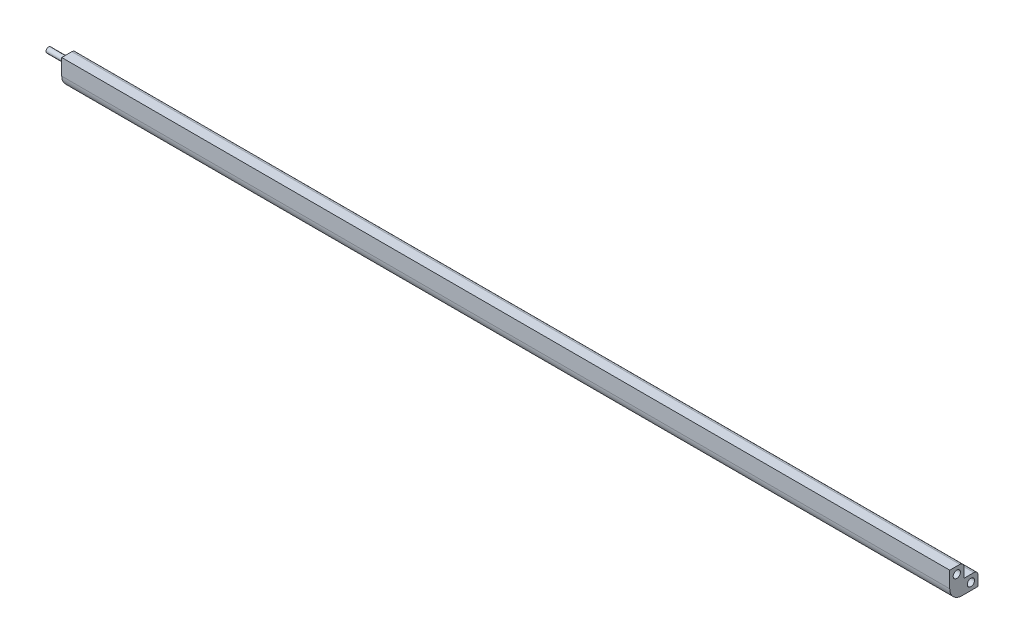
SolidWorks part; units mm, degrees
ref_plane "Front Plane" through (0, 0, 0) normal (0, 0, 1) x (1, 0, 0)
ref_plane "Top Plane" through (0, 0, 0) normal (0, 1, 0) x (1, 0, 0)
ref_plane "Right Plane" through (0, 0, 0) normal (1, 0, 0) x (0, 0, -1)
sketch "Sketch1" plane through (-29.2126, 0, 0) normal (1, 0, 0) x (0, 0, -1)
  line L1 (11.4452, 34.4708) -> (4.4452, 34.4708)
  line L2 (-25.0548, 34.4708) -> (6.4452, 34.4708) construction
  line L3 (4.4452, 34.4708) -> (4.4452, 27.4708)
  line L4 (4.4452, 27.4708) -> (11.4452, 27.4708)
  line L5 (11.4452, 29.4708) -> (11.4452, -30.5292) construction
  line L7 (11.4452, 27.4708) -> (11.4452, 34.4708)
  line L8 (7.9452, 34.4708) -> (7.9452, 30.9708)
  line L9 (7.9452, 30.9708) -> (11.4452, 30.9708)
  circle A0 centre (6.1952, 32.7208) radius 0.65
  circle A1 centre (9.6952, 29.2208) radius 0.65
  circle A2 centre (6.1952, 32.7208) radius 0.9
  circle A3 centre (9.6952, 29.2208) radius 0.9
  line M11 (11.4452, -30.5292) -> (11.4452, 29.4708)
  arc M12 (11.4452, 29.4708) -> (11.2149, 30.9708) centre (6.4452, 29.4708) ccw
  line M13 (6.4452, 34.4708) -> (-25.0548, 34.4708)
  dimension "D5" = 1.3
  dimension "D6" = 1.8
  dimension "D7" = 1.3
  dimension "D8" = 1.8
  dimension "D1" = 7
  dimension "D2" = 7
  dimension "D3" = 1.75
  dimension "D4" = 1.75
  dimension "D9" = 1.75
  dimension "D10" = 1.75
extrude "Boss-Extrude1" add sketch "Sketch1" along normal blind 220 contours L9 L8 L3 L4 A3 A2 M12 M13 M11 | L9 L7 M12 | L8 L1 M12 | A0 | A2 A0 | A3 A1 | A1 region at (-29.2126, 30.2926, -7.2532) region at (-29.2126, 30.5975, -11.3764) region at (-29.2126, 32.7208, -6.1952) region at (-29.2126, 29.2208, -9.6952) region at (-29.2126, 32.7208, -5.3206) region at (-29.2126, 29.2208, -8.8206)
sketch "Sketch2" plane through (190.7874, 0, 0) normal (1, 0, 0) x (0, 0, -1)
  line L0 (11.4452, 34.4708) -> (4.4452, 34.4708)
  line L1 (4.4452, 34.4708) -> (4.4452, 27.4708)
  line L2 (4.4452, 27.4708) -> (11.4452, 27.4708)
  line L3 (11.4452, 27.4708) -> (11.4452, 34.4708)
  line L4 (7.9452, 34.4708) -> (7.9452, 30.9708)
  line L5 (7.9452, 30.9708) -> (11.4452, 30.9708)
  line L6 (7.9452, 34.4708) -> (4.4452, 34.4708) construction
  line L7 (-25.0548, 34.4708) -> (6.4452, 34.4708) construction
  line L8 (11.4452, 27.4708) -> (11.4452, 30.9708) construction
  circle A0 centre (6.1952, 32.7208) radius 0.65
  circle A1 centre (9.6952, 29.2208) radius 0.65
  circle A2 centre (6.1952, 32.7208) radius 0.9
  circle A3 centre (9.6952, 29.2208) radius 0.9
  dimension "D5" = 1.3
  dimension "D6" = 1.8
  dimension "D7" = 1.3
  dimension "D8" = 1.8
  dimension "D1" = 7
  dimension "D2" = 7
  dimension "D3" = 1.75
  dimension "D4" = 1.75
  dimension "D9" = 1.75
  dimension "D10" = 1.75
extrude "Cut-Extrude1" cut sketch "Sketch2" against normal blind 6 contours A2 A0 | A0 | A3 A1 | A1 | A3 region at (190.7874, 32.7208, -6.1952) region at (190.7874, 29.2208, -9.6952) region at (190.7874, 32.7208, -5.3206) region at (190.7874, 29.2208, -8.8206)
extrude "Boss-Extrude2" add sketch "Sketch1<3>" against normal blind 5 contours A0 | A1 region at (-29.2126, 32.7208, -6.1952) region at (-29.2126, 29.2208, -9.6952)
sketch "Sketch1<3>" plane through (-29.2126, 0, 0) normal (1, 0, 0) x (0, 0, -1) same geometry as "Sketch1"
fillet "Fillet1" radius 3 1 edges at (80.7874, 27.4708, -4.4452)
fillet "Fillet2" radius 1 2 edges at (80.7874, 30.9708, -11.4452) (80.7874, 34.4708, -7.9452)
